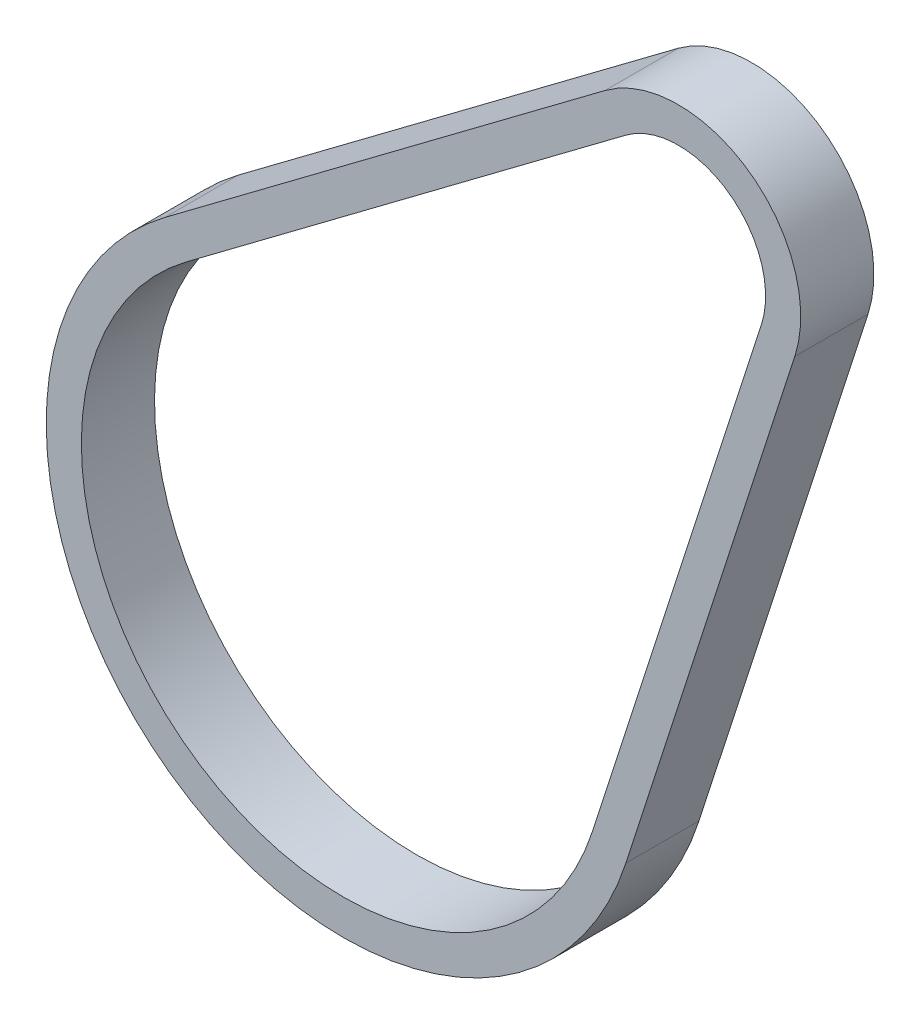
SolidWorks part; units mm, degrees
material "Rubber"
ref_plane "Front Plane" through (0, 0, 0) normal (0, 0, 1) x (1, 0, 0)
ref_plane "Top Plane" through (0, 0, 0) normal (0, 1, 0) x (1, 0, 0)
ref_plane "Right Plane" through (0, 0, 0) normal (1, 0, 0) x (0, 0, -1)
sketch "Sketch2" plane through (0, 0, 0) normal (0, 0, 1) x (1, 0, 0)
  line L0 (0, 0) -> (1, 0) construction
  line L1 (0, 0) -> (0, 1) construction
  line L2 (29.7221, 29.8917) -> (18.1745, -5.8688)
  line L3 (-11.4565, 15.2809) -> (18.6105, 37.8228)
  arc A0 (18.6105, 37.8228) -> (29.7221, 29.8917) centre (22.9067, 32.0925) cw
  arc A1 (18.1745, -5.8688) -> (-11.4565, 15.2809) centre (0, 0) cw
extrude "Extrude-Thin1" add sketch "Sketch2" against normal blind 5 thin thin type two direction wall 1.2 second wall 1.2
